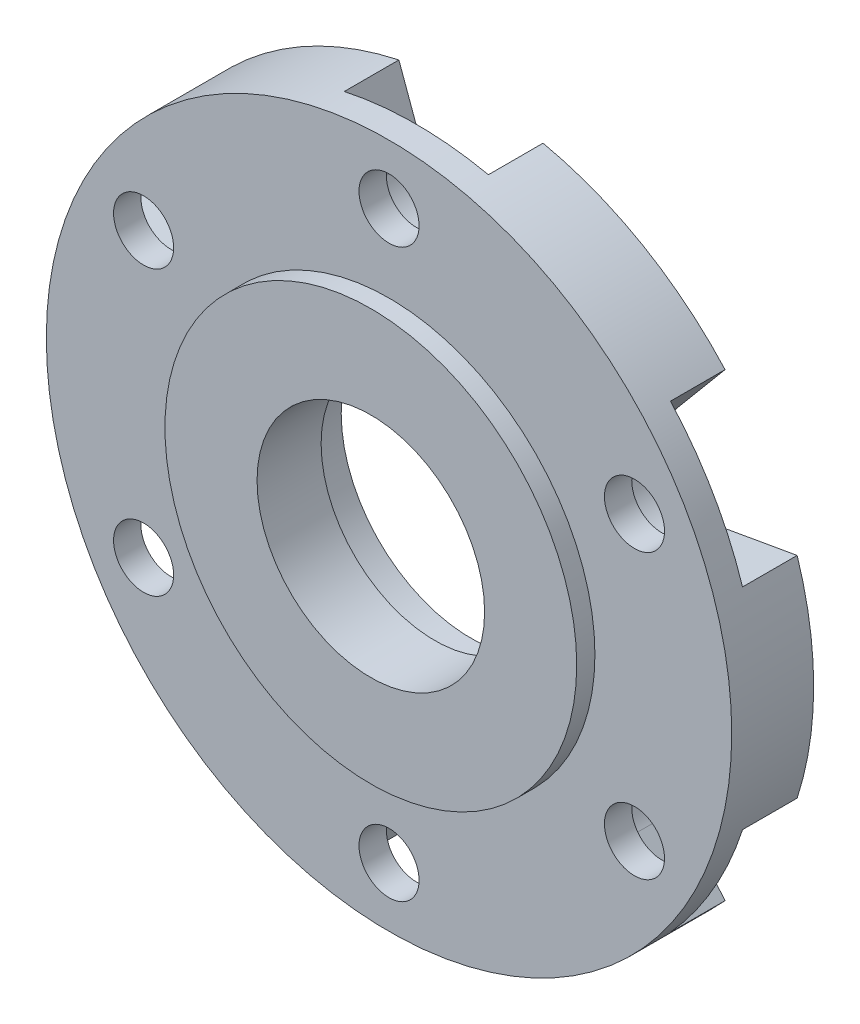
SolidWorks part; units mm, degrees
material "6061-T6 (SS)"
ref_plane "Front Plane" through (0, 0, 0) normal (0, 0, 1) x (1, 0, 0)
ref_plane "Top Plane" through (0, 0, 0) normal (0, 1, 0) x (1, 0, 0)
ref_plane "Right Plane" through (0, 0, 0) normal (1, 0, 0) x (0, 0, -1)
sketch "Sketch Spindle Skeleton" plane through (0, 0, 0) normal (1, 0, 0) x (0, 0, -1)
  line L0 (-95.847, -9.5) -> (-144, -9.5)
  line L5 (-1000, 0) -> (49000, 0)
  line L6 (0, -9.5) -> (0, 9.5)
  line L13 (0, 9.5) -> (-45.847, 9.5)
  line L26 (-45.847, 9.5) -> (-45.847, 14)
  line L27 (-45.847, 14) -> (-95.847, 14)
  line L32 (-95.847, 14) -> (-95.847, 9.5)
  line L34 (-160, 7) -> (-160, -7)
  line L36 (-95.847, -9.5) -> (-95.847, -14)
  line L37 (-95.847, -14) -> (-45.847, -14)
  line L38 (-45.847, -14) -> (-45.847, -9.5)
  line L39 (0, -9.5) -> (-45.847, -9.5)
  line L40 (-25.305, 37.6491) -> (-16.305, 37.6491)
  line L41 (-111.341, 22.6187) -> (-95.847, 22.6187)
  line L42 (-111.341, 22.6187) -> (-111.341, -22.6187)
  line L43 (-111.341, -22.6187) -> (-95.847, -22.6187)
  line L44 (-95.847, 22.6187) -> (-95.847, -22.6187)
  line L45 (-111.341, 22.6187) -> (-95.847, -22.6187) construction
  line L46 (-111.341, -22.6187) -> (-95.847, 22.6187) construction
  line L47 (-30.353, 22.6187) -> (-45.847, 22.6187)
  line L48 (-30.353, 22.6187) -> (-30.353, -22.6187)
  line L49 (-30.353, -22.6187) -> (-45.847, -22.6187)
  line L50 (-45.847, 22.6187) -> (-45.847, -22.6187)
  line L51 (-30.353, 22.6187) -> (-45.847, -22.6187) construction
  line L52 (-30.353, -22.6187) -> (-45.847, 22.6187) construction
  line L59 (-16.305, 37.6491) -> (-16.305, -37.6491)
  line L60 (-16.305, -37.6491) -> (-25.305, -37.6491)
  line L61 (-25.305, -22.6187) -> (-27.305, -22.6187)
  line L62 (-27.305, -22.6187) -> (-27.305, -12.5)
  line L63 (-27.305, -12.5) -> (-25.305, -12.5)
  line L64 (-25.305, -12.5) -> (-25.305, 12.5)
  line L65 (-25.305, 12.5) -> (-27.305, 12.5)
  line L66 (-27.305, 12.5) -> (-27.305, 22.6187)
  line L67 (-27.305, 22.6187) -> (-25.305, 22.6187)
  line L68 (-25.305, 22.6187) -> (-25.305, 37.6491)
  line L69 (-25.305, -22.6187) -> (-25.305, -37.6491)
  line L71 (-119.469, 37.6491) -> (-26.305, 37.6491)
  line L72 (-119.469, 37.6491) -> (-119.469, -37.6491)
  line L73 (-119.469, -37.6491) -> (-26.305, -37.6491)
  line L74 (-26.305, 37.6491) -> (-26.305, -37.6491)
  line L75 (-119.469, 37.6491) -> (-26.305, -37.6491) construction
  line L76 (-119.469, -37.6491) -> (-26.305, 37.6491) construction
  line L77 (-144, -9.5) -> (-144, -7)
  line L78 (-144, -7) -> (-160, -7)
  line L79 (-95.847, 9.5) -> (-144, 9.5)
  line L80 (-144, 7) -> (-160, 7)
  line L81 (-144, 9.5) -> (-144, 7)
  line L82 (-119.9235, 9.5) -> (-119.9235, -9.5) construction
  line L83 (-22.9235, 9.5) -> (-22.9235, -9.5) construction
  line L96 (-119.469, 37.6491) -> (-128.469, 37.6492)
  line L98 (-119.469, -37.6491) -> (-128.469, -37.6491)
  line L99 (-128.469, 37.6492) -> (-128.469, -37.6491)
  line L110 (-119.469, 37.6491) -> (-119.469, -37.6491)
  point P3 (0, 0)
  point P18 (-103.594, 0)
  point P24 (-38.1, 0)
  point P29 (-72.887, 0)
  point P48 (-16.305, 31.1339)
  point P70 (-128.469, 31.1339)
revolve "Main Revolve" add sketch "Sketch Spindle Skeleton" angle 360 about L5 region at (0, 23.3435, 20.997) region at (0, 17.5594, 26.805)
sketch "Sketch Center Cut" plane through (0, 0, 25.305) normal (0, 0, 1) x (1, 0, 0)
  circle A3 centre (0, 0) radius 12.5
  dimension "D1" = 25
extrude "Cut Center" cut sketch "Sketch Center Cut" against normal through all both and the other way through all
hole_wizard "CBORE for M6 SHCS1" positions "Hole wizard sketch 1" profile "Hole wizard sketch 2" counterbore size "M6" standard "ANSI Metric" end condition through all
sketch "Hole wizard sketch 1" plane through (0, 0, 16.305) normal (0, 0, -1) x (-1, 0, 0)
  point P0 (0, 31.1339)
sketch "Hole wizard sketch 2" plane through (0, 31.1339, 16.305) normal (1, 0, 0) x (0, 1, 0)
  line L0 (0, 0) -> (0, 11)
  line L1 (0, 11) -> (3.3, 11)
  line L3 (3.3, 11) -> (3.3, 6)
  line L4 (3.3, 6) -> (5.5, 6)
  line L5 (5.5, 6) -> (5.5, 0)
  line L7 (5.5, 0) -> (0, 0)
  line L11 (0, -6.35) -> (0, 107.95) construction
  dimension "Thru Hole Dia." = 6.6
  dimension "Thru Hole Depth" = 11
  dimension "C'Bore Dia." = 11
  dimension "C'Bore Depth" = 6
pattern_circular "CirPattern1" count 6 over 360 about axis through (0, 0, 16.305) along (0, 0, 1) of "CBORE for M6 SHCS1"
sketch "Sketch1" plane through (0, 0, 16.305) normal (0, 0, -1) x (-1, 0, 0)
  circle A0 centre (0, 0) radius 14.2558
  dimension "D1" = 28.5115
extrude "Cut-Extrude1" cut sketch "Sketch1" against normal blind 3.9624
sketch "Sketch2" plane through (0, 0, 16.305) normal (0, 0, -1) x (-1, 0, 0)
  line L0 (-5.1683, 29.2528) -> (-7.9179, 36.8071)
  line L1 (0, 31.1339) -> (0, 37.65) construction
  line L2 (5.1683, 29.2528) -> (7.9179, 36.8071)
  circle A0 centre (0, 31.1339) radius 5.5 construction
  circle A1 centre (0, 0) radius 37.6491 construction
  arc A2 (-5.1683, 29.2528) -> (5.1683, 29.2528) centre (0, 31.1339) ccw
  point P37 (0.065, 0.0375)
  circle M8 centre (0, 31.1339) radius 5.5
  circle M9 centre (0, 0) radius 37.6491
  dimension "D1" = 20
extrude "Cut-Extrude2" cut sketch "Sketch2" against normal up to surface (6 mm away) contours L1 L2 M8 M9 | L1 L0 M8 M9 region at (4.7304, 35.5149, 16.305) region at (-4.7304, 35.5149, 16.305) up to face at (23.6628, -15.567, 22.305)
pattern_circular "CirPattern2" count 6 over 360 about axis through (0, 0, 1000) along (0, 0, 1) of "Cut-Extrude2" reverse direction yes
